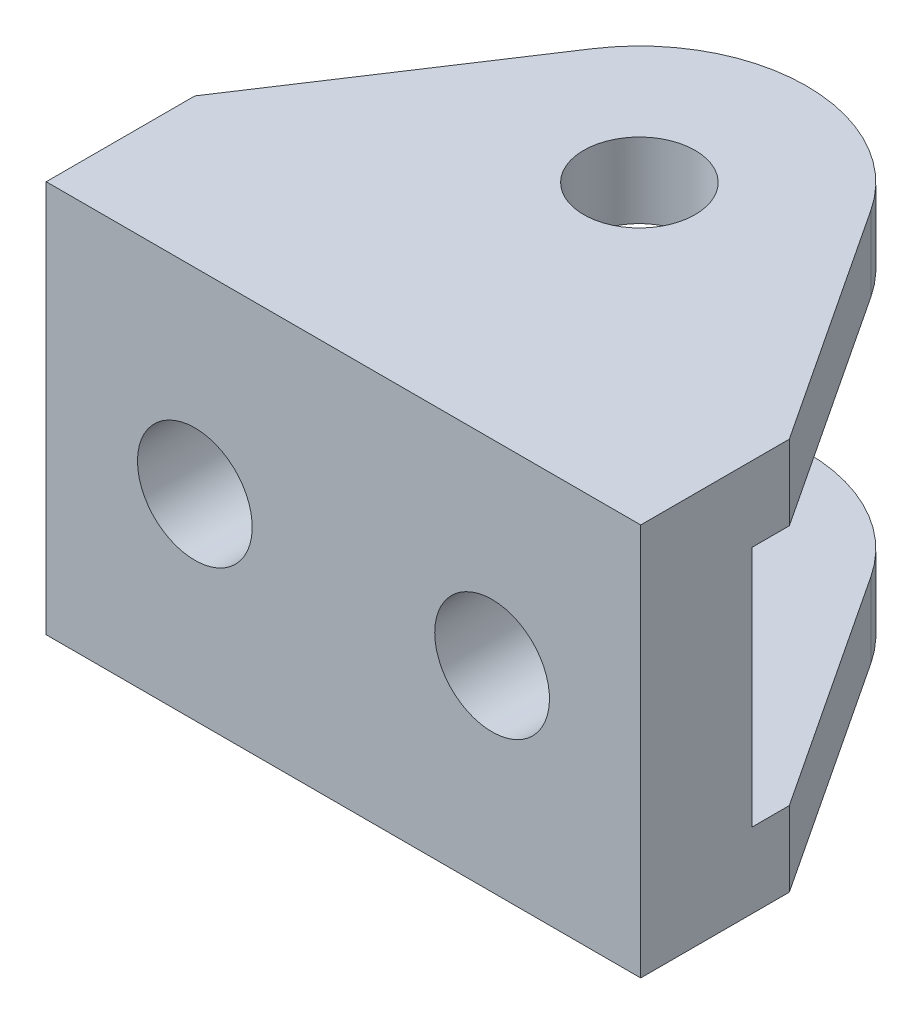
SolidWorks part; units mm, degrees
material "6061-T6 (SS)"
ref_plane "Front Plane" through (0, 0, 0) normal (0, 0, 1) x (1, 0, 0)
ref_plane "Top Plane" through (0, 0, 0) normal (0, 1, 0) x (1, 0, 0)
ref_plane "Right Plane" through (0, 0, 0) normal (1, 0, 0) x (0, 0, -1)
sketch "Sketch1" plane through (0, 0, 0) normal (1, 0, 0) x (0, 0, -1)
  line L0 (41.7969, 27.1145) -> (9.4996, 27.1145)
  line L1 (0, 0) -> (41.7969, 0)
  line L2 (0, 0) -> (0, 33.528)
  line L3 (0, 33.528) -> (41.7969, 33.528)
  line L4 (41.7969, 0) -> (41.7969, 6.4135)
  line L5 (9.4996, 27.1145) -> (9.4996, 6.4135)
  line L6 (9.4996, 6.4135) -> (41.7969, 6.4135)
  line L7 (41.7969, 27.1145) -> (41.7969, 33.528)
  line L8 (25.2869, 33.528) -> (25.2869, 0) construction
  dimension "D2" = 33.528
  dimension "D3" = 20.701
  dimension "D4" = 9.4996
  dimension "D5" = 16.51
extrude "Boss-Extrude1" add sketch "Sketch1" along normal blind 50.8
sketch "Sketch2" plane through (0, 0, -9.4996) normal (0, 0, -1) x (-1, 0, 0)
  line L0 (-25.4, 27.1145) -> (-25.4, 6.4135) construction
  line L1 (-50.8, 27.1145) -> (0, 27.1145) construction
  line L2 (-50.8, 6.4135) -> (0, 6.4135) construction
  line L3 (-38.1, 16.764) -> (-12.7, 16.764) construction
  circle A0 centre (-38.1, 16.764) radius 4.9022
  circle A1 centre (-12.7, 16.764) radius 4.9022
  point P8 (-25.4, 16.764)
  dimension "D2" = 9.8044
  dimension "D3" = 9.8044
  dimension "D1" = 25.4
extrude "3/8 Clearnace Holes" cut sketch "Sketch2" against normal up to surface (9.4996 mm away) up to face at (25.4, 16.764, 0)
sketch "Sketch3" plane through (0, 0, 0) normal (0, -1, 0) x (1, 0, 0)
  line L0 (0, -12.7) -> (13.4685, -33.1464)
  line L1 (0, 0) -> (0, -41.7969) construction
  line L2 (37.3315, -33.1464) -> (50.8, -12.7)
  line L3 (50.8, 0) -> (50.8, -41.7969) construction
  line L4 (50.8, 0) -> (0, 0) construction
  line L6 (0, -12.7) -> (0, -41.7969)
  line L7 (0, -41.7969) -> (50.8, -41.7969)
  line L8 (50.8, -41.7969) -> (50.8, -12.7)
  arc A0 (13.4685, -33.1464) -> (37.3315, -33.1464) centre (25.4, -25.2869) ccw
  circle A1 centre (25.4, -25.2869) radius 4.7625
  dimension "D3" = 9.525
  dimension "D4" = 9.525
  dimension "D1" = 12.7
  dimension "D2" = 12.7
extrude "Cut-Extrude2" cut sketch "Sketch3" against normal up to surface (33.528 mm away) up to face at (25.4, 33.528, -20.8985)
equation "\"1inch\"=62.1211"
